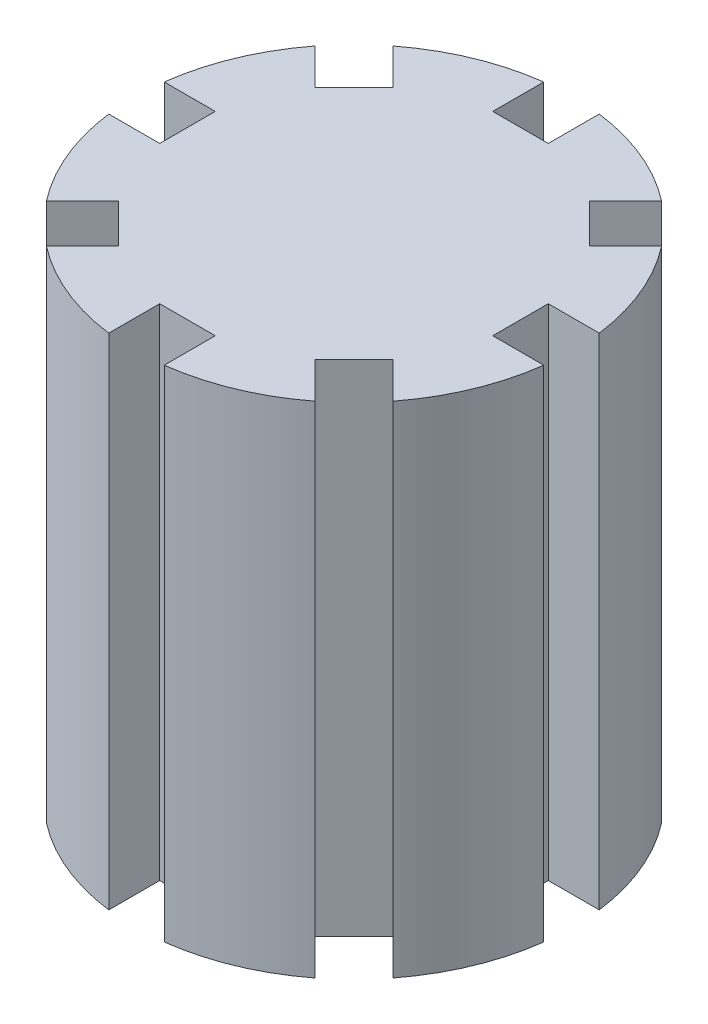
SolidWorks part; units mm, degrees
material "ABS"
ref_plane "Front Plane" through (0, 0, 0) normal (0, 0, 1) x (1, 0, 0)
ref_plane "Top Plane" through (0, 0, 0) normal (0, 1, 0) x (1, 0, 0)
ref_plane "Right Plane" through (0, 0, 0) normal (1, 0, 0) x (0, 0, -1)
sketch "Sketch1" plane through (0, 0, 0) normal (0, 1, 0) x (1, 0, 0)
  circle A0 centre (0, 0) radius 3.95
  circle A1 centre (0, 0) radius 2.375
  dimension "D1" = 7.9
  dimension "D2" = 4.75
extrude "Boss-Extrude1" add sketch "Sketch1" along normal blind 5 contours A1 | A0 A1 region at (-3.8383, 0, 0) region at (0, 0, 0)
extrude "Boss-Extrude2" add sketch "Sketch1<3>" against normal blind 4 contours A0 A1 region at (-3.8383, 0, 0)
sketch "Sketch1<3>" plane through (0, 0, 0) normal (0, 1, 0) x (1, 0, 0) same geometry as "Sketch1"
sketch "Sketch2" plane through (0, -4, 0) normal (0, -1, 0) x (1, 0, 0)
  line L1 (-0.5, 4) -> (0.5, 4)
  line L2 (-0.5, 4) -> (-0.5, 3)
  line L3 (-0.5, 3) -> (0.5, 3)
  line L4 (0.5, 4) -> (0.5, 3)
  point P4 (0, 4)
  point P260 (0, 0)
  dimension "D1" = 3
  dimension "D2" = 1
  dimension "D3" = 1
extrude "Cut-Extrude1" cut sketch "Sketch2" against normal through all
pattern_circular "CirPattern1" count 8 over 360 about axis through (0, -4, 0) along (0, 1, 0) of "Cut-Extrude1"
